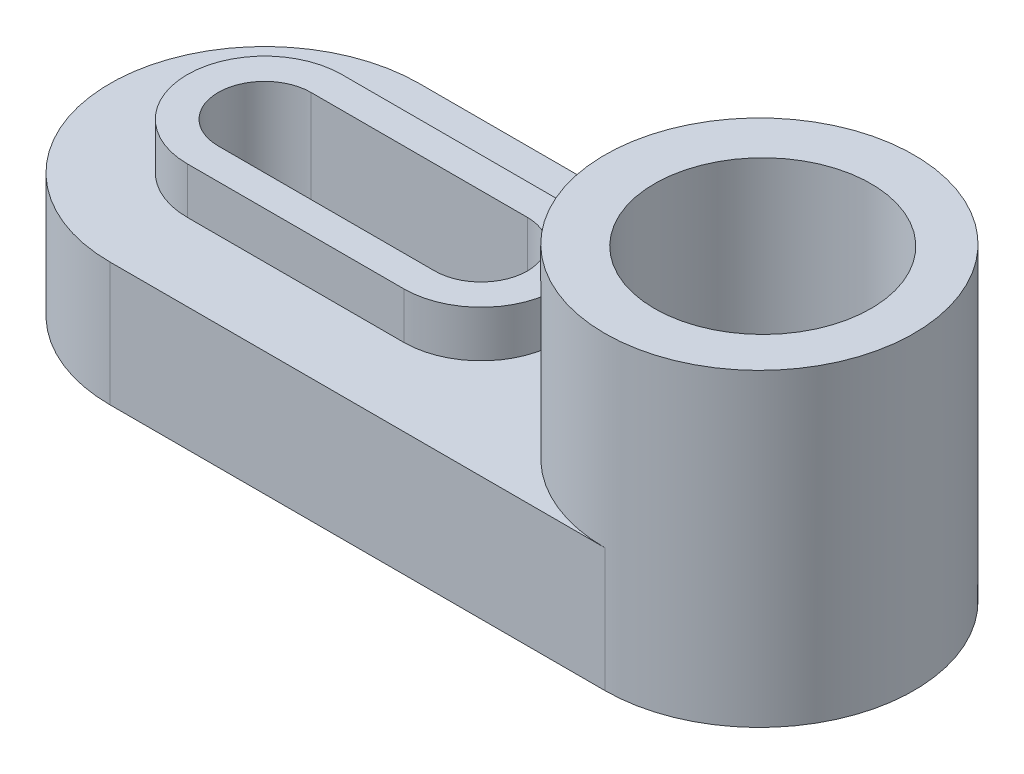
SolidWorks part; units mm, degrees
ref_plane "前视基准面" through (0, 0, 0) normal (0, 0, 1) x (1, 0, 0)
ref_plane "上视基准面" through (0, 0, 0) normal (0, 1, 0) x (1, 0, 0)
ref_plane "右视基准面" through (0, 0, 0) normal (1, 0, 0) x (0, 0, -1)
other "Configuration Table"
sketch "草图2" plane through (0, 0, 0) normal (0, 1, 0) x (1, 0, 0)
  line L0 (-16, 0) -> (16, 0) construction
  line L1 (-16, 10) -> (16, 10)
  line L2 (-16, -10) -> (16, -10)
  arc A0 (-16, 10) -> (-16, -10) centre (-16, 0) ccw
  arc A1 (16, -10) -> (16, 10) centre (16, 0) ccw
  circle A2 centre (16, 0) radius 10
  point P2 (0, 0)
  dimension "D1" = 10
  dimension "D2" = 32
extrude "凸台-拉伸1" add sketch "草图2" along normal blind 20 contours A1 A2 region at (16, 0, 0)
extrude "凸台-拉伸2" add sketch "草图2<3>" along normal blind 8 contours A2 L1 A0 L2 region at (-7.854, 0, 0)
sketch "草图2<3>" plane through (0, 0, 0) normal (0, 1, 0) x (1, 0, 0) same geometry as "草图2"
sketch "草图7" plane through (0, 0, 0) normal (0, 1, 0) x (1, 0, 0)
  line L0 (-16, 0) -> (-2, 0) construction
  line L1 (-16, 5) -> (-2, 5)
  line L2 (-16, -5) -> (-2, -5)
  line L3 (-16, 0) -> (-2, 0) construction
  line L4 (-16, 3) -> (-2, 3)
  line L5 (-16, -3) -> (-2, -3)
  arc A0 (-16, 5) -> (-16, -5) centre (-16, 0) ccw
  arc A1 (-2, -5) -> (-2, 5) centre (-2, 0) ccw
  arc A2 (-16, 3) -> (-16, -3) centre (-16, 0) ccw
  arc A3 (-2, -3) -> (-2, 3) centre (-2, 0) ccw
  circle A4 centre (16, 0) radius 10 construction
  point P2 (-9, 0)
  point P9 (-9, 0)
  point P17 (0, 0)
  point P18 (-9, 0)
  point P19 (-13.3705, 0)
  point P20 (0, 0)
  point P21 (-2, -3)
  point P22 (0, 0)
  point P23 (-16, 0)
  point P24 (0, 0)
  point P25 (0, 0)
  point P26 (-16, 0)
  point P27 (0, 0)
  point P28 (0, 0)
  dimension "D3" = 5
  dimension "D4" = 3
  dimension "D1" = 18
  dimension "D2" = 14
extrude "凸台-拉伸3" add sketch "草图7" along normal blind 11
extrude "切除-拉伸7" cut sketch "草图7<6>" along normal through all both and the other way through all contours L5 A3 L4 A2 region at (-9, 0, 0)
sketch "草图7<6>" plane through (0, 0, 0) normal (0, 1, 0) x (1, 0, 0) same geometry as "草图7"
hole_wizard "Ø1.0mm 暗销孔1" positions "草图12" profile "草图13" hole size "Ø1.0" standard "GB" end condition through all
sketch "草图12" plane through (0, 20, 0) normal (0, 1, 0) x (1, 0, 0)
  point P0 (16.2184, 0)
sketch "草图13" plane through (16.2184, 20, 0) normal (1, 0, 0) x (0, 0, 1)
  line L0 (0, 0) -> (0, 20)
  line L1 (0, 20) -> (7, 20)
  line L2 (7, 20) -> (7, 0)
  line L3 (7, 0) -> (0.525, 0)
  line L5 (0.525, 0) -> (0, 0)
  line L6 (-7, 0) -> (-0.525, 0) construction
  line L11 (0, -6.35) -> (0, 107.95) construction
  dimension "通孔孔直径" = 14
  dimension "通孔孔深度" = 20
  dimension "近端锥形沉头孔直径" = 14
  dimension "近端锥形沉头孔角度" = 180
